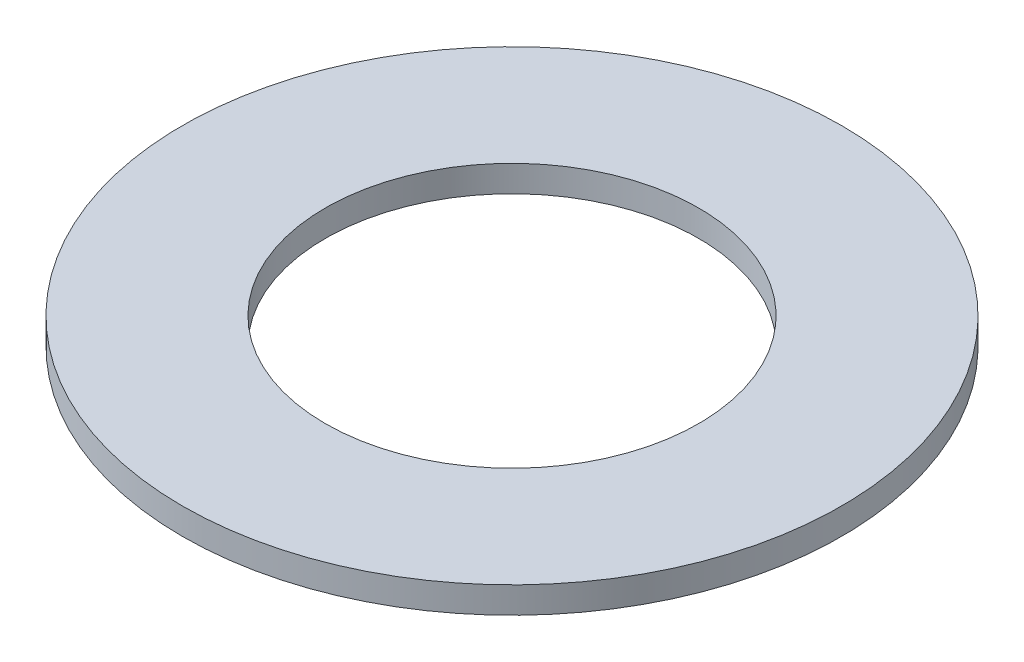
SolidWorks part; units mm, degrees
ref_plane "Front Plane" through (0, 0, 0) normal (0, 0, 1) x (1, 0, 0)
ref_plane "Top Plane" through (0, 0, 0) normal (0, 1, 0) x (1, 0, 0)
ref_plane "Right Plane" through (0, 0, 0) normal (1, 0, 0) x (0, 0, -1)
sketch "Sketch1" plane through (0, 0, 0) normal (0, 1, 0) x (1, 0, 0)
  circle A0 centre (0, 0) radius 75
  dimension "FLANGE_OD" = 150
extrude "Boss-Extrude1" add sketch "Sketch1" along normal blind 6
sketch "Sketch2" plane through (0, 0, 0) normal (0, 1, 0) x (1, 0, 0)
  circle A0 centre (0, 0) radius 42.5
  dimension "BORE_D" = 85
extrude "Cut-Extrude1" cut sketch "Sketch2" along normal through all
sketch "Sketch3" plane through (0, 6, 0) normal (0, 1, 0) x (1, 0, 0)
  circle A0 centre (0, 0) radius 33.8367 construction
  circle A1 centre (-33.8367, 0) radius 4.5318
  dimension "BOLT_D" = 9.0636
  dimension "BOLT_PCD" = 67.6735
extrude "Cut-Extrude2" cut sketch "Sketch3" against normal blind 5.0572 rebuild error yes
pattern_circular "CirPattern1" count 8 over 360 rebuild error yes
